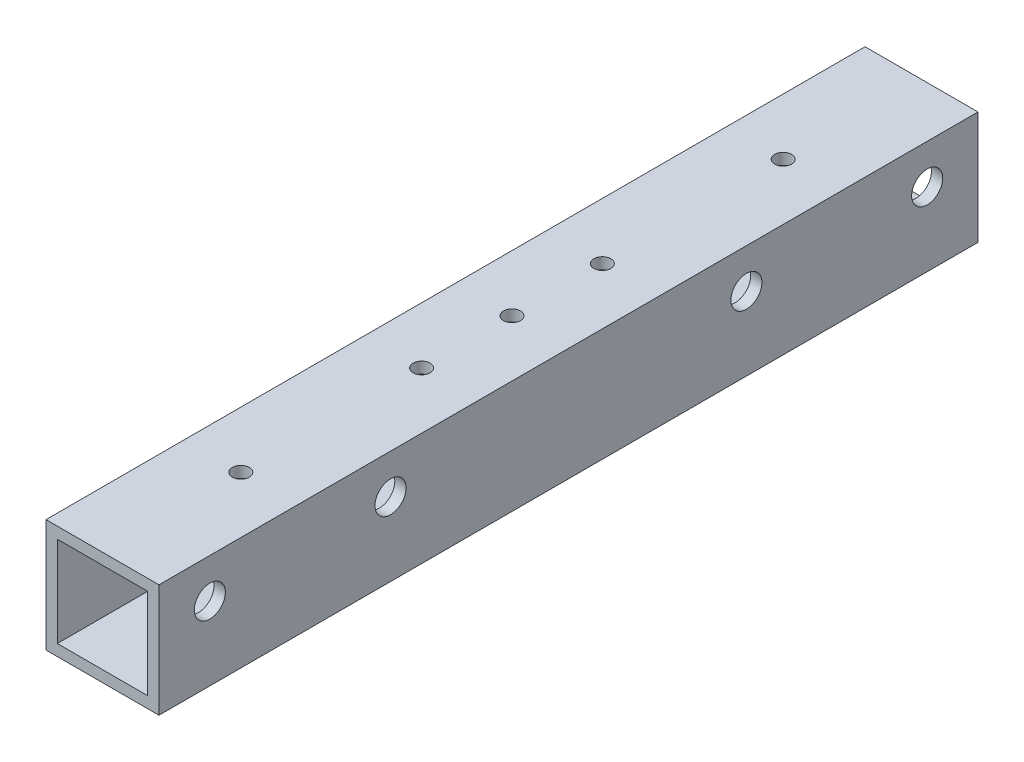
SolidWorks part; units mm, degrees
ref_plane "前视基准面" through (0, 0, 0) normal (0, 0, 1) x (1, 0, 0)
ref_plane "上视基准面" through (0, 0, 0) normal (0, 1, 0) x (1, 0, 0)
ref_plane "右视基准面" through (0, 0, 0) normal (1, 0, 0) x (0, 0, -1)
other "Configuration Table"
sketch "草图1" plane through (0, 0, 0) normal (0, 0, 1) x (1, 0, 0)
  line L1 (-10, -10) -> (10, -10)
  line L2 (-10, -10) -> (-10, 10)
  line L3 (-10, 10) -> (10, 10)
  line L4 (10, -10) -> (10, 10)
  line L5 (-10, -10) -> (10, 10) construction
  line L6 (-10, 10) -> (10, -10) construction
  line L7 (-8, -8) -> (8, -8)
  line L8 (-8, -8) -> (-8, 8)
  line L9 (-8, 8) -> (8, 8)
  line L10 (8, -8) -> (8, 8)
  line L11 (-8, -8) -> (8, 8) construction
  line L12 (-8, 8) -> (8, -8) construction
  point P0 (0, 0)
  point P6 (0, 0)
  dimension "D1" = 20
  dimension "D2" = 20
  dimension "D3" = 2
  dimension "D4" = 2
extrude "凸台-拉伸1" add sketch "草图1" along normal blind 145
sketch "草图2" plane through (10, 0, 0) normal (1, 0, 0) x (0, 0, -1)
  line L0 (-145, -10) -> (-145, 10) construction
  line L1 (-145, 10) -> (0, 10) construction
  line L2 (-72.5, -10) -> (-72.5, 10) construction
  line L3 (-145, -10) -> (0, -10) construction
  circle A0 centre (-136, 3) radius 2.75
  circle A1 centre (-104, 3) radius 2.75
  circle A2 centre (-9, 3) radius 2.75
  circle A3 centre (-41, 3) radius 2.75
  dimension "D1" = 5.5
  dimension "D3" = 13
  dimension "D4" = 32
  dimension "D2" = 9
extrude "切除-拉伸1" cut sketch "草图2" against normal up to surface (20 mm away) up to face at (-10, 0, 72.5)
sketch "草图3" plane through (0, -10, 0) normal (0, -1, 0) x (1, 0, 0)
  line L0 (0, 0) -> (0, 145) construction
  line L1 (-10, 145) -> (10, 145) construction
  circle A0 centre (0, 72.5) radius 1.5
  circle A1 centre (0, 88.5) radius 1.5
  circle A2 centre (0, 120.5) radius 1.5
  circle A3 centre (0, 56.5) radius 1.5
  circle A4 centre (0, 24.5) radius 1.5
  dimension "D1" = 3
  dimension "D2" = 16
  dimension "D3" = 16
  dimension "D4" = 32
  dimension "D5" = 32
extrude "切除-拉伸2" cut sketch "草图3" against normal up to surface (20 mm away) up to face at (0, 10, 72.5)
